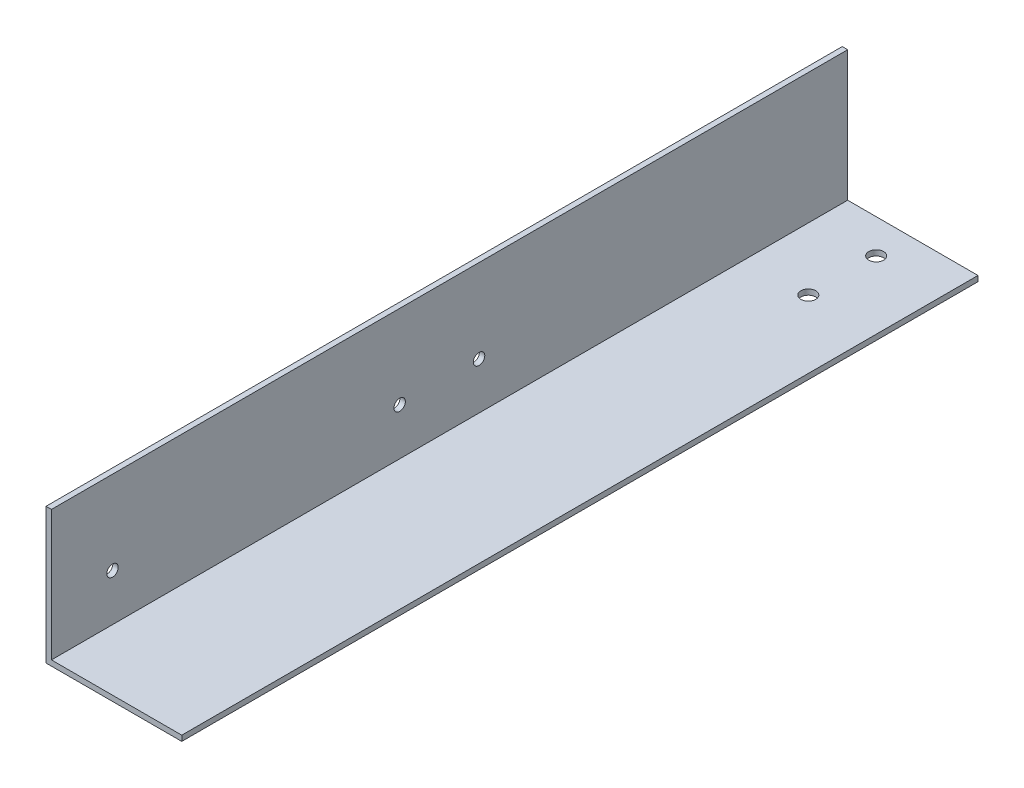
SolidWorks part; units mm, degrees
ref_plane "Front Plane" through (0, 0, 0) normal (0, 0, 1) x (1, 0, 0)
ref_plane "Top Plane" through (0, 0, 0) normal (0, 1, 0) x (1, 0, 0)
ref_plane "Right Plane" through (0, 0, 0) normal (1, 0, 0) x (0, 0, -1)
sketch "Sketch1" plane through (0, 0, 0) normal (0, 0, 1) x (1, 0, 0)
  line L0 (0, 0) -> (50, 0)
  line L1 (50, 0) -> (50, 2)
  line L2 (50, 2) -> (2, 2)
  line L3 (2, 2) -> (2, 50)
  line L4 (2, 50) -> (0, 50)
  line L5 (0, 50) -> (0, 0)
  dimension "D1" = 50
  dimension "D2" = 50
  dimension "D3" = 2
  dimension "D4" = 2
extrude "Boss-Extrude1" add sketch "Sketch1" along normal blind 293.25
sketch "Sketch2" plane through (0, 0, 0) normal (1, 0, 0) x (0, 0, -1)
  circle A0 centre (-135.75, 19.25) radius 2.1
  circle A1 centre (-165, 19.25) radius 2.1
  circle A2 centre (-270.75, 19.25) radius 2.1
  dimension "D1" = 4.2
  dimension "D2" = 19.25
  dimension "D3" = 135.75
  dimension "D4" = 165
  dimension "D5" = 270.75
extrude "Cut-Extrude1" cut sketch "Sketch2" against normal mid plane 10
sketch "Sketch3" plane through (0, 0, 0) normal (0, 1, 0) x (1, 0, 0)
  circle A0 centre (25, -12.5) radius 2.75
  circle A1 centre (25, -37.5) radius 2.75
  dimension "D1" = 5.5
  dimension "D2" = 25
  dimension "D3" = 12.5
  dimension "D4" = 37.5
extrude "Cut-Extrude2" cut sketch "Sketch3" against normal mid plane 10
